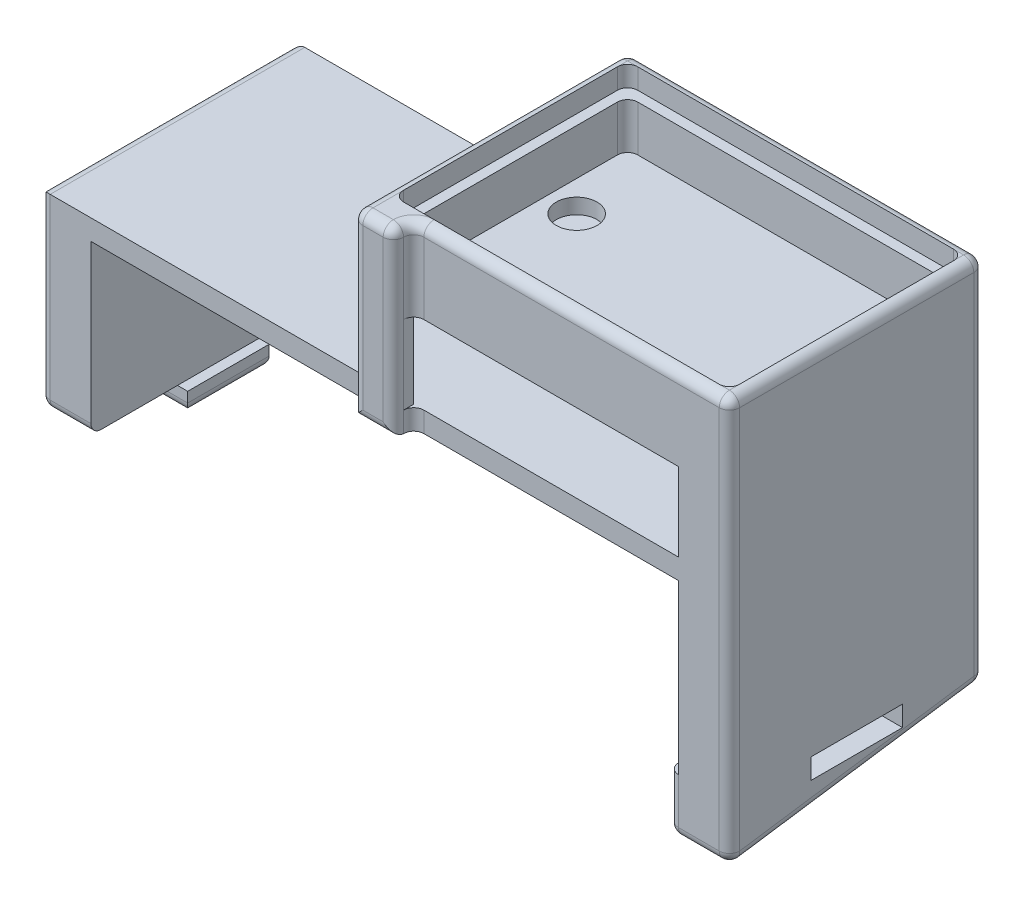
SolidWorks part; units mm, degrees
ref_plane "Front Plane" through (0, 0, 0) normal (0, 0, 1) x (1, 0, 0)
ref_plane "Top Plane" through (0, 0, 0) normal (0, 1, 0) x (1, 0, 0)
ref_plane "Right Plane" through (0, 0, 0) normal (1, 0, 0) x (0, 0, -1)
sketch "Sketch1" plane through (0, 0, 0) normal (0, 0, 1) x (1, 0, 0)
  line L0 (0, 0) -> (30, 0)
  line L1 (30, 0) -> (30, -7.7)
  line L2 (30, -7.7) -> (-32.7, -7.7)
  line L3 (-32.7, -7.7) -> (-32.7, -26.2)
  line L4 (-32.7, -26.2) -> (35, -26.2)
  line L5 (35, -26.2) -> (35, 8)
  line L6 (35, 8) -> (0, 8)
  line L7 (0, 8) -> (0, 0)
  dimension "D1" = 7.7
  dimension "D2" = 30
  dimension "D3" = 35
  dimension "D4" = 67.7
  dimension "D5" = 8
  dimension "D6" = 18.5
extrude "Boss-Extrude1" add sketch "Sketch1" along normal blind 25
sketch "Sketch2" plane through (0, 0, 25) normal (0, 0, 1) x (1, 0, 0)
  line L0 (-32.7, -26.2) -> (35, -26.2) construction
  line L1 (30, -26.2) -> (-27.7, -26.2)
  line L2 (30, -26.2) -> (30, -9.7)
  line L3 (30, -9.7) -> (-27.7, -9.7)
  line L4 (-27.7, -26.2) -> (-27.7, -9.7)
  line L5 (35, -26.2) -> (35, 8) construction
  dimension "D1" = 57.7
  dimension "D2" = 5
  dimension "D3" = 16.5
extrude "Cut-Extrude1" cut sketch "Sketch2" against normal through all
sketch "Sketch3" plane through (0, 8, 0) normal (0, 1, 0) x (1, 0, 0)
  line L0 (35, -25) -> (35, 0) construction
  line L1 (2, -2) -> (33, -2)
  line L2 (2, -2) -> (2, -23)
  line L3 (2, -23) -> (33, -23)
  line L4 (33, -2) -> (33, -23)
  line L5 (0, -25) -> (0, 0) construction
  line L6 (35, 0) -> (0, 0) construction
  line L7 (35, -25) -> (0, -25) construction
  dimension "D1" = 2
  dimension "D2" = 2
  dimension "D3" = 2
  dimension "D4" = 2
extrude "Cut-Extrude2" cut sketch "Sketch3" against normal blind 6.5
sketch "Sketch4" plane through (0, -26.2, 0) normal (0, -1, 0) x (1, 0, 0)
  line L0 (35, 12.5) -> (35.1733, 12.5) construction
  line L1 (35, 25) -> (35, 0) construction
  line L2 (30, 0) -> (30, 25) construction
  circle A0 centre (30.5, 12.5) radius 2
  dimension "D1" = 4
  dimension "D2" = 0.5
extrude "Cut-Extrude3" cut sketch "Sketch4" against normal up to surface (27.7 mm away) up to face at (17.5, 1.5, 12.5)
sketch "Sketch5" plane through (0, 1.5, 0) normal (0, 1, 0) x (1, 0, 0)
  line L0 (35, -25) -> (0, -25) construction
  line L2 (30, -25) -> (30, -14.4365) construction
  circle A0 centre (5, -10) radius 2
  dimension "D1" = 4
  dimension "D2" = 25
  dimension "D3" = 15
extrude "Cut-Extrude4" cut sketch "Sketch5" against normal up to surface (1.5 mm away) up to face at (19.75, 0, 12.5)
sketch "Sketch6" plane through (0, -26.2, 0) normal (0, -1, 0) x (1, 0, 0)
  line L0 (35, 25) -> (35, 0) construction
  line L1 (35, 25) -> (29, 25)
  line L2 (35, 25) -> (35, 17)
  line L3 (35, 17) -> (29, 17)
  line L4 (29, 25) -> (29, 17)
  line L5 (35, 0) -> (29, 0)
  line L6 (35, 0) -> (35, 8)
  line L7 (35, 8) -> (29, 8)
  line L8 (29, 0) -> (29, 8)
  line L9 (-32.7, 25) -> (-32.7, 0) construction
  line L10 (-32.7, 16.5) -> (-26.7, 16.5)
  line L11 (-32.7, 16.5) -> (-32.7, 8.5)
  line L12 (-32.7, 8.5) -> (-26.7, 8.5)
  line L13 (-26.7, 16.5) -> (-26.7, 8.5)
  line L14 (35, 12.5) -> (36.5966, 12.5) construction
  dimension "D1" = 8
  dimension "D2" = 6
extrude "Boss-Extrude2" add sketch "Sketch6" along normal blind 2
sketch "Sketch7" plane through (0, 0, 25) normal (0, 0, 1) x (1, 0, 0)
  line L0 (0, 8) -> (0, -9.7)
  line L1 (35, 8) -> (0, 8) construction
  line L3 (30, -9.7) -> (-27.7, -9.7) construction
  line L4 (4, -9.7) -> (4, 8)
  line L5 (4, 8) -> (0, 8)
  line L20 (30, -9.7) -> (30, -26.2)
  line L21 (30, -26.2) -> (29, -26.2)
  line L22 (29, -26.2) -> (29, -28.2)
  line L23 (29, -28.2) -> (35, -28.2)
  line L24 (35, -28.2) -> (35, 8)
  line L25 (35, 8) -> (0, 8)
  line L26 (0, 8) -> (0, 0)
  line L27 (0, 0) -> (30, 0)
  line L28 (30, 0) -> (30, -7.7)
  line L29 (30, -7.7) -> (-32.7, -7.7)
  line L30 (-32.7, -7.7) -> (-32.7, -26.2)
  line L31 (-32.7, -26.2) -> (-27.7, -26.2)
  line L32 (-27.7, -26.2) -> (-27.7, -9.7)
  line L33 (-27.7, -9.7) -> (30, -9.7)
  line L47 (0, -9.7) -> (4, -9.7)
  dimension "D2" = 4
  dimension "D1" = 0
extrude "Boss-Extrude3" add sketch "Sketch7" along normal blind 2
sketch "Sketch8" plane through (35, 0, 0) normal (1, 0, 0) x (0, 0, -1)
  line L0 (0, -28.2) -> (-25, -31.8607)
  line L2 (-25, -31.8607) -> (-25, -28.2)
  line L3 (-25, -28.2) -> (-25, 8) construction
  line L4 (-25, -28.2) -> (0, -28.2)
  line L5 (0, -28.2) -> (-8, -28.2) construction
  dimension "D1" = 8.331
  dimension "D2" = 3.6607
extrude "Boss-Extrude4" add sketch "Sketch8" against normal up to surface (6 mm away) up to face at (29, -27.2, 4)
sketch "Sketch9" plane through (0, 8, 0) normal (0, 1, 0) x (1, 0, 0)
  line L0 (33, -23) -> (33, -2) construction
  line L1 (34, -24) -> (1, -24)
  line L2 (34, -24) -> (34, -1)
  line L3 (34, -1) -> (1, -1)
  line L4 (1, -24) -> (1, -1)
  line L5 (2, -23) -> (33, -23) construction
  line L6 (2, -2) -> (2, -23) construction
  line L7 (33, -2) -> (2, -2) construction
  dimension "D1" = 1
  dimension "D2" = 1
  dimension "D3" = 1
  dimension "D4" = 1
extrude "Cut-Extrude5" cut sketch "Sketch9" against normal blind 2
fillet "Fillet1" radius 1 8 edges at (34, 7, 1) (1, 7, 1) (1, 7, 24) (34, 7, 24) (33, 3.75, 2) (2, 3.75, 2) (2, 3.75, 23) (33, 3.75, 23)
fillet "Fillet2" radius 1 34 edges at (0, 8, 13.5) (17.5, 8, 0) (35, 8, 12.5) (29, -29.0304, 25) (29, -27.2, 0) (29, -30.0304, 12.5) (35, -30.0304, 12.5) (-30.2, -26.2, 0) (-30.2, -26.2, 25) (-29.7, -28.2, 8.5) (-29.7, -28.2, 16.5) (-32.7, -27.2, 8.5) (-32.7, -27.2, 16.5) (-32.7, -26.2, 20.75) (-32.7, -28.2, 12.5) (-32.7, -26.2, 4.25) (-32.7, -7.7, 12.5) (-32.7, -16.95, 0) (-32.7, -16.95, 25) (35, -10.1, 0) (35, -11.9304, 25) (0, -0.85, 27) (0, 4, 0) (4, -0.85, 27) (2, -9.7, 27) (2, 8, 27) (32, -31.8607, 25) (32, -28.2, 0) (-26.7, -28.2, 12.5)
sketch "Sketch10" plane through (-27.7, 0, 0) normal (1, 0, 0) x (0, 0, -1)
  line L0 (-12.5, -9.7) -> (-12.5, -2.753) construction
  line L1 (0, -9.7) -> (-25, -9.7) construction
  circle A0 centre (-14, -12.05) radius 1
  circle A1 centre (-11, -12.05) radius 1
  dimension "D2" = 2
  dimension "D3" = 2
  dimension "D1" = 3
  dimension "D4" = 2.35
extrude "Boss-Extrude5" add sketch "Sketch10" along normal blind 1.5
fillet "Fillet3" radius 1 2 edges at (-26.2, -12.05, 13) (-26.2, -12.05, 10)
